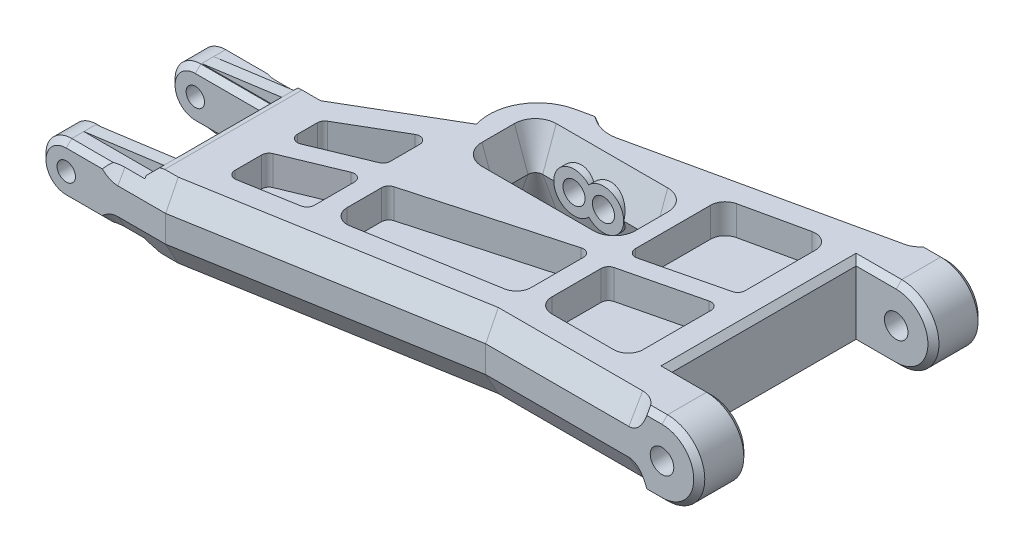
SolidWorks part; units mm, degrees
ref_plane "Front Plane" through (0, 0, 0) normal (0, 0, 1) x (1, 0, 0)
ref_plane "Top Plane" through (0, 0, 0) normal (0, 1, 0) x (1, 0, 0)
ref_plane "Right Plane" through (0, 0, 0) normal (1, 0, 0) x (0, 0, -1)
sketch "Sketch1" plane through (0, 0, 0) normal (0, 0, 1) x (1, 0, 0)
  line L0 (0, 0) -> (74.5, 0) construction
  line L1 (0, 5.06) -> (74.5, 5.06)
  line L2 (0, -5.06) -> (74.5, -5.06)
  line L3 (74.5, 0) -> (73.5, 0) construction
  line L4 (74.5, -3.5) -> (73.5, -3.5)
  line L5 (74.5, 3.5) -> (73.5, 3.5)
  line L6 (73.5, 3.5) -> (63, 5.06)
  line L7 (55, 0) -> (-55, 0) construction
  line L8 (73.5, -3.5) -> (63, -5.06)
  line L9 (37.25, 0) -> (37.25, -5.06) construction
  line L10 (0, 0) -> (1, 0) construction
  line L11 (0, -3.5) -> (1, -3.5)
  line L12 (0, 3.5) -> (1, 3.5)
  line L13 (1, 3.5) -> (11.5, 5.06)
  line L14 (1, -3.5) -> (11.5, -5.06)
  arc A0 (0, 5.06) -> (0, -5.06) centre (0, 0) ccw
  arc A1 (74.5, -5.06) -> (74.5, 5.06) centre (74.5, 0) ccw
  arc A2 (74.5, -3.5) -> (74.5, 3.5) centre (74.5, 0) ccw
  arc A3 (73.5, 3.5) -> (73.5, -3.5) centre (73.5, 0) ccw
  arc A4 (0, -3.5) -> (0, 3.5) centre (0, 0) cw
  arc A5 (1, 3.5) -> (1, -3.5) centre (1, 0) cw
  point P3 (37.25, 0)
  point P10 (74, 0)
  point P21 (78, 0)
  point P26 (0.5, 0)
  dimension "D1" = 5.06
  dimension "D3" = 3.5
  dimension "D2" = 74.5
  dimension "D4" = 1
  dimension "D5" = 15
extrude "Boss-Extrude1" add sketch "Sketch1" along normal mid plane 45 contours A3 L6 L1 A0 L2 L8 | L5 A3 L4 A2 | A2 L4 L8 L2 A1 L1 L6 L5 | A5 L12 A4 L11
sketch "Sketch2" plane through (0, 5.06, 0) normal (0, 1, 0) x (1, 0, 0)
  line L0 (13.5, -22.5) -> (50.56, -16.1)
  line L1 (11.5, -22.5) -> (74.5, -22.5) construction
  line L2 (50.56, -16.1) -> (79.56, -16.1)
  line L3 (1, -22.5) -> (11.5, -22.5) construction
  line L4 (79.56, -16.1) -> (79.56, -22.5)
  line L5 (79.56, -22.5) -> (13.5, -22.5)
  line L6 (-4.3, -0.1) -> (13.5, -0.1)
  line L7 (11.5, 22.5) -> (74.5, 22.5) construction
  line L8 (13.5, -0.1) -> (27.06, 7.8417)
  line L9 (32.2529, 14.3) -> (69.56, 22.5)
  line L10 (-3.5, 22.5) -> (-3.5, -22.5) construction
  line L11 (69.56, 22.5) -> (-4.3, 22.5)
  line L12 (-4.3, 22.5) -> (-4.3, -0.1)
  line L13 (-4.3, -0.1) -> (-4.3, -22.5) construction
  line L14 (-4.3, -4.97) -> (9.7, -4.97)
  line L15 (-4.3, -4.97) -> (-4.3, -17.63)
  line L16 (-4.3, -17.63) -> (9.7, -17.63)
  line L17 (9.7, -4.97) -> (9.7, -17.63)
  line L18 (79.56, -22.5) -> (79.56, 22.5) construction
  line L19 (27.06, 7.8417) -> (27.06, -20.1583) construction
  line L21 (69.06, -9.3) -> (79.56, -9.3)
  line L22 (69.06, -9.3) -> (69.06, 15.7)
  line L23 (69.06, 15.7) -> (79.56, 15.7)
  line L24 (79.56, -9.3) -> (79.56, 15.7)
  line L25 (69.06, -9.3) -> (79.56, 15.7) construction
  line L26 (69.06, 15.7) -> (79.56, -9.3) construction
  arc A0 (32.2529, 14.3) -> (27.06, 7.8417) centre (33.6724, 7.8417) ccw
  point P5 (74.31, 3.2)
  point P20 (-4.3, -11.3)
  line M25 (74.5, -22.5) -> (74.5, 22.5)
  dimension "D1" = 22.4
  dimension "D2" = 29
  dimension "D3" = 38.6
  dimension "D4" = 17.8
  dimension "D5" = 12.66
  dimension "D6" = 14
  dimension "D7" = 17
  dimension "D8" = 14.4
  dimension "D9" = 10
  dimension "D10" = 52.5
  dimension "D11" = 28
  dimension "D12" = 6.8
  dimension "D13" = 25
  dimension "D14" = 10.5
extrude "Cut-Extrude1" cut sketch "Sketch2" against normal through all contours L23 L22 L21 M25 | L21 L24 L23 M25 | L8 A0 L9 L11 L12 L6 | L15 L14 L17 L16 | L5 L0 L2 L4
sketch "Sketch3" plane through (0, 5.06, 0) normal (0, 1, 0) x (1, 0, 0)
  line L0 (16.38, -17.1823) -> (16.38, -11.6823)
  line L1 (16.38, -4.2077) -> (25.88, 1.3562)
  line L2 (25.88, 1.3562) -> (25.88, -5.0352)
  line L3 (16.38, -17.1823) -> (25.88, -15.5418)
  line L4 (52.78, -11.35) -> (65.18, -11.35)
  line L5 (65.18, -11.35) -> (65.18, 1.15)
  line L6 (65.18, 16.5408) -> (52.78, 13.8153)
  line L7 (52.78, 13.8153) -> (52.78, 0.7221)
  line L8 (28.38, -15.11) -> (50.28, -11.328)
  line L9 (9.7, -4.97) -> (9.7, -17.63) construction
  line L10 (13.5, -22.5) -> (50.56, -16.1) construction
  line L11 (16.38, -11.6823) -> (25.88, -7.7418)
  line L12 (28.38, -15.11) -> (28.38, -7.31)
  line L13 (28.38, -7.31) -> (50.28, -1.228)
  line L14 (50.28, -11.328) -> (50.28, -1.228)
  line L15 (52.78, -1.85) -> (65.18, 1.15)
  line L16 (16.38, -8.9758) -> (25.88, -5.0352)
  line L17 (13.5, -0.1) -> (27.06, 7.8417) construction
  line L18 (32.2529, 14.3) -> (69.56, 22.5) construction
  line L19 (50.56, -16.1) -> (74.5, -16.1) construction
  line L20 (52.78, 0.7221) -> (65.18, 3.7221)
  line L21 (52.78, -1.85) -> (52.78, -11.35)
  line L22 (65.18, 3.7221) -> (65.18, 16.5408)
  line L23 (25.88, -7.7418) -> (25.88, -15.5418)
  line L24 (16.38, -8.9758) -> (16.38, -4.2077)
  dimension "D1" = 9.5
  dimension "D2" = 6.68
  dimension "D3" = 4.75
  dimension "D4" = 2.5
  dimension "D5" = 7.8
  dimension "D6" = 10.1
  dimension "D7" = 9.5
  dimension "D8" = 33.9
  dimension "D9" = 48.8
  dimension "D10" = 2.5
  dimension "D11" = 2.5
  dimension "D12" = 5.5
  dimension "D13" = 7.8
  dimension "D14" = 5
  dimension "D15" = 4.88
  dimension "D16" = 4.75
  dimension "D17" = 12.5
  dimension "D18" = 2.5
extrude "Cut-Extrude2" cut sketch "Sketch3" against normal blind 4
sketch "Sketch4" plane through (0, 0, 0) normal (0, 1, 0) x (1, 0, 0)
  line L0 (-3.5, -0.1) -> (-3.5, -4.97) construction
  line L1 (32.7, 9.5) -> (47.83, 9.5)
  line L2 (31.7, 8.5) -> (31.7, 4.1)
  line L3 (32.7, 3.1) -> (47.83, 3.1)
  line L4 (48.83, 8.5) -> (48.83, 4.1)
  line L5 (31.7, 9.5) -> (48.83, 3.1) construction
  line L6 (31.7, 3.1) -> (48.83, 9.5) construction
  arc A0 (47.83, 9.5) -> (48.83, 8.5) centre (47.83, 8.5) cw
  arc A1 (47.83, 3.1) -> (48.83, 4.1) centre (47.83, 4.1) ccw
  arc A2 (31.7, 4.1) -> (32.7, 3.1) centre (32.7, 4.1) ccw
  arc A3 (32.7, 9.5) -> (31.7, 8.5) centre (32.7, 8.5) ccw
  point P0 (40.265, 6.3)
  dimension "D5" = 1
  dimension "D1" = 17.13
  dimension "D2" = 6.4
  dimension "D3" = 4.8
  dimension "D4" = 35.2
extrude "Cut-Extrude3" cut sketch "Sketch4" against normal through all draft 20 and the other way through all draft 20
sketch "Sketch5" plane through (0, 0, 0.1) normal (0, 0, -1) x (-1, 0, 0)
  circle A0 centre (0, 0) radius 1.25
extrude "Cut-Extrude4" cut sketch "Sketch5" against normal through all
sketch "Sketch6" plane through (0, 0, -22.5) normal (0, 0, -1) x (-1, 0, 0)
  circle A0 centre (-74.5, 0) radius 1.6
extrude "Cut-Extrude5" cut sketch "Sketch6" against normal through all
sketch "Sketch7" plane through (0, 0, 22.5) normal (0, 0, 1) x (1, 0, 0)
  line L0 (1, 3.5) -> (11.5, 5.06) construction
  line L1 (-3.5, 4.7926) -> (9.7, 4.7926)
  line L2 (-3.5, 4.7926) -> (-3.5, 3.5)
  line L3 (-3.5, 3.5) -> (9.7, 3.5)
  line L4 (9.7, 4.7926) -> (9.7, 3.5)
  line L5 (-3.5, 4.7926) -> (9.7, 3.5) construction
  line L6 (-3.5, 3.5) -> (9.7, 4.7926) construction
  arc A0 (0, 3.5) -> (0, -3.5) centre (0, 0) ccw construction
  point P0 (3.1, 4.1463)
  point P5 (-3.5, 0)
  point P6 (0, 0)
  point P13 (0, 0)
  point P14 (0, 0)
  dimension "D2" = 3.5
chamfer "Chamfer1" distance 3.25 angle 30 3 edges at (50.9065, 5.06, -18.4) (20.28, 5.06, -3.8709) (12.5, 5.06, 0.1)
chamfer "Chamfer4" distance 3.25 angle 30 3 edges at (62.53, 5.06, 16.1) (32.03, 5.06, 19.3) (12.5, 5.06, 22.5)
extrude "Cut-Extrude6" cut sketch "Sketch7" against normal through all
chamfer "Chamfer3" distance 1 angle 45 1 edges at (9.7, 4.7926, 11.3)
sketch "Sketch8" plane through (0, 0, 16.1) normal (0, 0, 1) x (1, 0, 0)
  line L0 (73, 0) -> (73, 5.06)
  line L1 (73, 5.06) -> (74.5, 5.06)
  circle A0 centre (74.5, 0) radius 5.06
  dimension "D1" = 1.5
extrude "Boss-Extrude2" add sketch "Sketch8" against normal up to surface
ref_plane "Plane1" through (0, 0, -3.2) normal (0, 0, -1) x (-1, 0, 0)
sketch "Sketch9" plane through (0, 0, -22.5) normal (0, 0, -1) x (-1, 0, 0)
  line L0 (-73, 0) -> (-73, 5.06) construction
  line L1 (-73, 5.06) -> (-74.5, 5.06) construction
  line L2 (-73, 0) -> (-73, 5.06)
  line L3 (-73, 5.06) -> (-74.5, 5.06)
  circle A1 centre (-74.5, 0) radius 5.06
  circle A2 centre (-74.5, 0) radius 5.06
  line M4 (-69.56, 1.81) -> (-76.8057, 4.5041)
  dimension "D1" = 0
extrude "Boss-Extrude3" add sketch "Sketch9" against normal up to surface contours L2 A2 M4 | A2 L2 L3
fillet "Fillet1" radius 3 2 edges at (73, 4.0745, -21.9175) (73, 3.435, 15.1618)
sketch "Sketch10" plane through (0, 0, 0) normal (0, 0, 1) x (1, 0, 0)
  circle A0 centre (36.9516, 0) radius 2.75
  circle A1 centre (40.9516, 0) radius 2.75
  arc A2 (-2.9956, 1.81) -> (0, -3.5) centre (0, 0) ccw construction
  point P1 (-3.0484, -1.7197)
  point P5 (0, 0)
  point P9 (40.5, 1.4572)
  dimension "D2" = 5.5
  dimension "D1" = 4
  dimension "D3" = 40
extrude "Boss-Extrude4" add sketch "Sketch10" against normal up to vertex (3.1 mm away) contours A0 | A1
sketch "Sketch11" plane through (0, 0, -3.1) normal (0, 0, -1) x (-1, 0, 0)
  circle A0 centre (-36.9516, 0) radius 1.5
  circle A1 centre (-40.9516, 0) radius 1.5
  dimension "D1" = 3
extrude "Cut-Extrude7" cut sketch "Sketch11" against normal blind 5
ref_plane "Plane2" through (0, 0, -9.5) normal (0, 0, 1) x (1, 0, 0)
ref_plane "Plane3" through (0, 0, -6.3) normal (0, 0, -1) x (-1, 0, 0)
mirror "Mirror2" about plane through (0, 0, -6.3) normal (0, 0, -1) of "Boss-Extrude4", "Cut-Extrude7"
ref_plane "Plane4" through (0, 0, -13.5) normal (0, 0, 1) x (1, 0, 0)
sketch "Sketch17" plane through (0, 5.06, 0) normal (0, 1, 0) x (1, 0, 0)
  line L0 (33.2296, 14.5147) -> (33.6324, 12.682)
  line L4 (28.1488, 11.4767) -> (70.5577, 20.7981)
  line L5 (70.5577, 20.7981) -> (70.5577, 22.5)
  line L6 (70.5577, 22.5) -> (69.56, 22.5)
  line L7 (69.56, 22.5) -> (32.2529, 14.3)
  line L8 (28.1488, 11.4767) -> (70.5577, 20.7981)
  line L9 (70.5577, 20.7981) -> (70.5577, 22.5)
  line L10 (70.5577, 22.5) -> (69.56, 22.5)
  line L11 (69.56, 22.5) -> (32.2529, 14.3)
  arc A1 (32.2529, 14.3) -> (28.1488, 11.4767) centre (33.6724, 7.8417) ccw
  arc A2 (32.2529, 14.3) -> (28.1488, 11.4767) centre (33.6724, 7.8417) ccw
  point P8 (0, 0)
  point P9 (37.3497, 15.4203)
  line M38 (70.5577, 20.7981) -> (28.1488, 11.4767)
  dimension "D2" = 1
  dimension "D1" = 0
extrude "Boss-Extrude5" add sketch "Sketch17" against normal up to surface (3.25 mm away) contours L11 A2 L0 M38
fillet "Fillet2" radius 5 1 edges at (33.431, 3.435, -13.5984)
sketch "Sketch12" plane through (0, 0, -13.5) normal (0, 0, 1) x (1, 0, 0)
  line L0 (36.9516, 0) -> (40.9516, 0) construction
  line L1 (36.9516, 2.95) -> (40.9516, 2.95)
  line L2 (36.9516, -2.95) -> (40.9516, -2.95)
  arc A0 (36.9516, 2.95) -> (36.9516, -2.95) centre (36.9516, 0) ccw
  arc A1 (40.9516, -2.95) -> (40.9516, 2.95) centre (40.9516, 0) ccw
  arc A2 (38.9516, 1.8875) -> (34.2016, 0) centre (36.9516, 0) ccw construction
  arc A3 (43.7016, 0) -> (38.9516, 1.8875) centre (40.9516, 0) ccw construction
  point P3 (38.9516, 0)
  point P14 (36.5, 3.5178)
  dimension "D1" = 5.9
extrude "Cut-Extrude8" cut sketch "Sketch12" against normal blind 5
ref_plane "Plane5" through (0, 0, 11.3) normal (0, 0, 1) x (1, 0, 0)
ref_plane "Plane6" through (0, 0, 19.3) normal (0, 0, 1) x (1, 0, 0)
sketch "Sketch13" plane through (0, 0, 19.3) normal (0, 0, 1) x (1, 0, 0)
  line L0 (0, 3.5) -> (10.8745, 4.9671)
  point P2 (0, 0)
extrude "Extrude-Thin1" add sketch "Sketch13" along normal mid plane 1.63 thin contours L0
sketch "Sketch18" plane through (0, 0, 22.5) normal (0, 0, 1) x (1, 0, 0)
  line L0 (2, 3.5) -> (2, 1.81)
  line L7 (11.5, 5.06) -> (10.8745, 4.9671)
  line L8 (10.8745, 4.9671) -> (9.7, 3.7926)
  line L9 (9.7, 3.7926) -> (9.7, 3.5)
  line L10 (9.7, 3.5) -> (0, 3.5)
  line L11 (-2.9956, 1.81) -> (13.5, 1.81)
  line L12 (13.5, 1.81) -> (13.3392, 5.06)
  line L13 (13.3392, 5.06) -> (11.5, 5.06)
  line L14 (11.5, 5.06) -> (10.8745, 4.9671)
  line L15 (10.8745, 4.9671) -> (9.7, 3.7926)
  line L16 (9.7, 3.7926) -> (9.7, 3.5)
  line L17 (9.7, 3.5) -> (0, 3.5)
  line L18 (-2.9956, 1.81) -> (13.5, 1.81)
  line L19 (13.5, 1.81) -> (13.3392, 5.06)
  line L20 (13.3392, 5.06) -> (11.5, 5.06)
  arc A1 (0, 3.5) -> (-2.9956, 1.81) centre (0, 0) ccw
  arc A2 (0, 3.5) -> (-2.9956, 1.81) centre (0, 0) ccw
  line M12 (13.5, 1.81) -> (-2.9956, 1.81)
  dimension "D2" = 2
  dimension "D1" = 0
extrude "Boss-Extrude6" add sketch "Sketch18" against normal up to surface (0.9757 mm away) contours L17 A2 L0 M12
sketch "Sketch19" plane through (0, 0, 0.1) normal (0, 0, -1) x (-1, 0, 0)
  line L0 (-2, 3.5) -> (-2, 1.81) construction
  line L1 (-2, 3.5) -> (-2, 1.81)
  line L7 (-10.8745, 4.9671) -> (-11.5, 5.06)
  line L8 (-9.7, 3.7926) -> (-10.8745, 4.9671)
  line L9 (-9.7, 3.5) -> (-9.7, 3.7926)
  line L10 (0, 3.5) -> (-9.7, 3.5)
  line L11 (-13.5, 1.81) -> (2.9956, 1.81)
  line L12 (-13.3392, 5.06) -> (-13.5, 1.81)
  line L13 (-11.5, 5.06) -> (-13.3392, 5.06)
  line L14 (-10.8745, 4.9671) -> (-11.5, 5.06)
  line L15 (-9.7, 3.7926) -> (-10.8745, 4.9671)
  line L16 (-9.7, 3.5) -> (-9.7, 3.7926)
  line L17 (0, 3.5) -> (-9.7, 3.5)
  line L18 (-13.5, 1.81) -> (2.9956, 1.81)
  line L19 (-13.3392, 5.06) -> (-13.5, 1.81)
  line L20 (-11.5, 5.06) -> (-13.3392, 5.06)
  arc A1 (2.9956, 1.81) -> (0, 3.5) centre (0, 0) ccw
  arc A2 (2.9956, 1.81) -> (0, 3.5) centre (0, 0) ccw
  line M11 (2.9956, 1.81) -> (-13.5, 1.81)
  dimension "D1" = 0
extrude "Boss-Extrude7" add sketch "Sketch19" against normal up to surface (0.9757 mm away) contours A2 L17 L1 M11
fillet "Fillet3" radius 5 2 edges at (2, 2.655, 22.0121) (2, 2.655, 0.5879)
mirror "Mirror3" about plane through (0, 0, 11.3) normal (0, 0, 1) of "Extrude-Thin1"
fillet "Fillet4" radius 2 6 edges at (52.78, 3.06, -13.8153) (28.38, 3.06, 15.11) (50.28, 3.06, 11.328) (52.78, 3.06, 11.35) (65.18, 3.06, 11.35) (65.18, 3.06, -16.5408)
fillet "Fillet5" radius 1 14 edges at (16.38, 3.06, 17.1823) (25.88, 3.06, 15.5418) (25.88, 3.06, 7.7418) (16.38, 3.06, 8.9758) (25.88, 3.06, 5.0352) (25.88, 3.06, -1.3562) (50.28, 3.06, 1.228) (52.78, 3.06, -0.7221) (16.38, 3.06, 4.2077) (16.38, 3.06, 11.6823) (28.38, 3.06, 7.31) (52.78, 3.06, 1.85) (65.18, 3.06, -1.15) (65.18, 3.06, -3.7221)
chamfer "Chamfer5" distance 0.75 angle 45 36 edges at (71.78, -5.06, -15.7) (71.78, 5.06, 9.3) (71.78, 5.06, -15.7) (79.56, 0, -15.7) (79.56, 0, 9.3) (71.78, -5.06, 9.3) (69.06, 5.06, -3.2) (79.56, 0, -22.5) (73.5832, 5.06, 16.1) (73.554, 5.06, -22.5) (71.5612, 2.6865, 16.1) (71.7442, 5.06, -21.3869) (72.03, -5.06, -22.5) (5.35, -4.1463, 4.97) (5.35, -4.1463, 17.63) (6.25, -4.28, 0.1) (2.1093, 3.5, 22.5) (2.1093, 3.5, 0.1) (12.5, -5.06, 22.5) (5.5466, 2.2418, 0.1) (5.5466, 3.5, 21.7736) (-3.5, 0, 0.1) (-3.5, 0, 22.5) (0.5, -3.5, 0.1) (12.5, -5.06, 0.1) (0.5, -3.5, 22.5) (4.85, 3.5, 17.63) (-3.5, 0, 17.63) (0.5, -3.5, 4.97) (0.5, -3.5, 17.63) (4.85, 3.5, 4.97) (-3.5, 0, 4.97) (6.25, -4.28, 22.5) (79.56, 0, 16.1) (62.53, -5.06, 16.1) (69.06, -5.06, -3.2)
sketch "Sketch20" plane through (0, 0, 0) normal (0, 1, 0) x (1, 0, 0)
  circle A0 centre (0, 0) radius 94.3985
extrude "Cut-Extrude10" cut sketch "Sketch20" against normal through all
mirror "Mirror4" about plane through (0, 0, 0) normal (0, 1, 0) of bodies 120
ref_plane "Plane7" through (0, 0, -3.2) normal (0, 0, 1) x (1, 0, 0)
